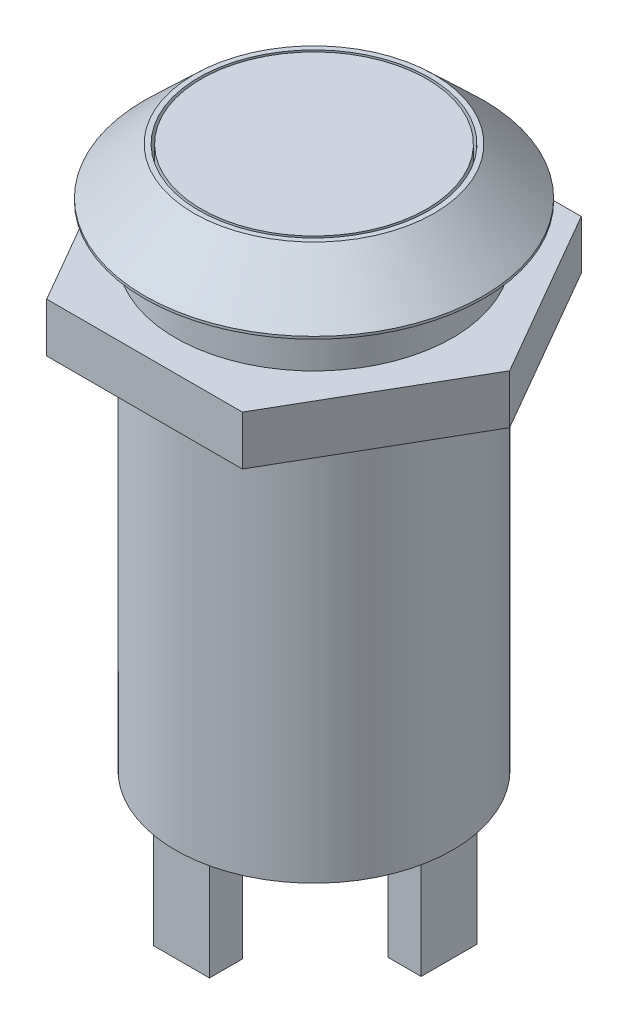
SolidWorks part; units mm, degrees
ref_plane "Front Plane" through (0, 0, 0) normal (0, 0, 1) x (1, 0, 0)
ref_plane "Top Plane" through (0, 0, 0) normal (0, 1, 0) x (1, 0, 0)
ref_plane "Right Plane" through (0, 0, 0) normal (1, 0, 0) x (0, 0, -1)
sketch "Sketch1" plane through (0, 0, 0) normal (0, 1, 0) x (1, 0, 0)
  circle A0 centre (0, 0) radius 5.625
  dimension "D1" = 11.25
extrude "Boss-Extrude1" add sketch "Sketch1" along normal blind 20
sketch "Sketch2" plane through (0, 20, 0) normal (0, 1, 0) x (1, 0, 0)
  circle A0 centre (0, 0) radius 6.875
  dimension "D1" = 13.75
extrude "Boss-Extrude2" add sketch "Sketch2" along normal blind 2
sketch "Sketch3" plane through (0, 22, 0) normal (0, 1, 0) x (1, 0, 0)
  circle A0 centre (0, 0) radius 4.625
  dimension "D1" = 9.25
extrude "Cut-Extrude-Thin1" cut sketch "Sketch3" against normal blind 2 thin thin type mid plane wall 0.1
chamfer "Chamfer1" distance 1.9 distance2 2 1 edges at (0, 22, 6.875) tangent propagation no first distance on face at (0, 22, 6.875)
sketch "Sketch4" plane through (0, 0, 0) normal (0, -1, 0) x (1, 0, 0)
  line L1 (3.9693, 6.875) -> (-3.9693, 6.875)
  line L2 (-3.9693, 6.875) -> (-7.9386, 0)
  line L3 (-7.9386, 0) -> (-3.9693, -6.875)
  line L4 (-3.9693, -6.875) -> (3.9693, -6.875)
  line L5 (3.9693, -6.875) -> (7.9386, 0)
  line L6 (7.9386, 0) -> (3.9693, 6.875)
  circle A1 centre (0, 0) radius 6.875 construction
  circle A2 centre (0, 0) radius 6.875 construction
  circle A3 centre (0, 0) radius 6.875 construction
extrude "Boss-Extrude5" add sketch "Sketch4" against normal blind 18
sketch "Sketch6" plane through (0, 0, 0) normal (0, -1, 0) x (1, 0, 0)
  line L6 (7.9386, 0) -> (3.9693, 6.875)
  line L7 (7.9386, 0) -> (3.9693, 6.875)
  line L8 (3.9693, -6.875) -> (7.9386, 0)
  line L9 (3.9693, -6.875) -> (7.9386, 0)
  line L10 (-3.9693, -6.875) -> (3.9693, -6.875)
  line L11 (-3.9693, -6.875) -> (3.9693, -6.875)
  line L12 (-7.9386, 0) -> (-3.9693, -6.875)
  line L13 (-7.9386, 0) -> (-3.9693, -6.875)
  line L14 (-3.9693, 6.875) -> (-7.9386, 0)
  line L15 (-3.9693, 6.875) -> (-7.9386, 0)
  line L16 (3.9693, 6.875) -> (-3.9693, 6.875)
  line L17 (3.9693, 6.875) -> (-3.9693, 6.875)
  circle A0 centre (0, 0) radius 5.625 construction
  circle A3 centre (0, 0) radius 5.625
  dimension "D1" = 0
extrude "Cut-Extrude1" cut sketch "Sketch6" against normal blind 16
sketch "Sketch5" plane through (0, 0, 0) normal (0, -1, 0) x (1, 0, 0)
  line L1 (-1.1868, -4.0862) -> (1.0806, -4.0862)
  line L2 (-1.1868, -4.0862) -> (-1.1868, -5.4273)
  line L3 (-1.1868, -5.4273) -> (1.0806, -5.4273)
  line L4 (1.0806, -4.0862) -> (1.0806, -5.4273)
extrude "Boss-Extrude4" add sketch "Sketch5" along normal blind 4 contours L2 L1 L4 L3
pattern_circular "CirPattern2" count 4 every 90 about axis through (0, 0, 0) along (0, -1, 0) of "Boss-Extrude4"
